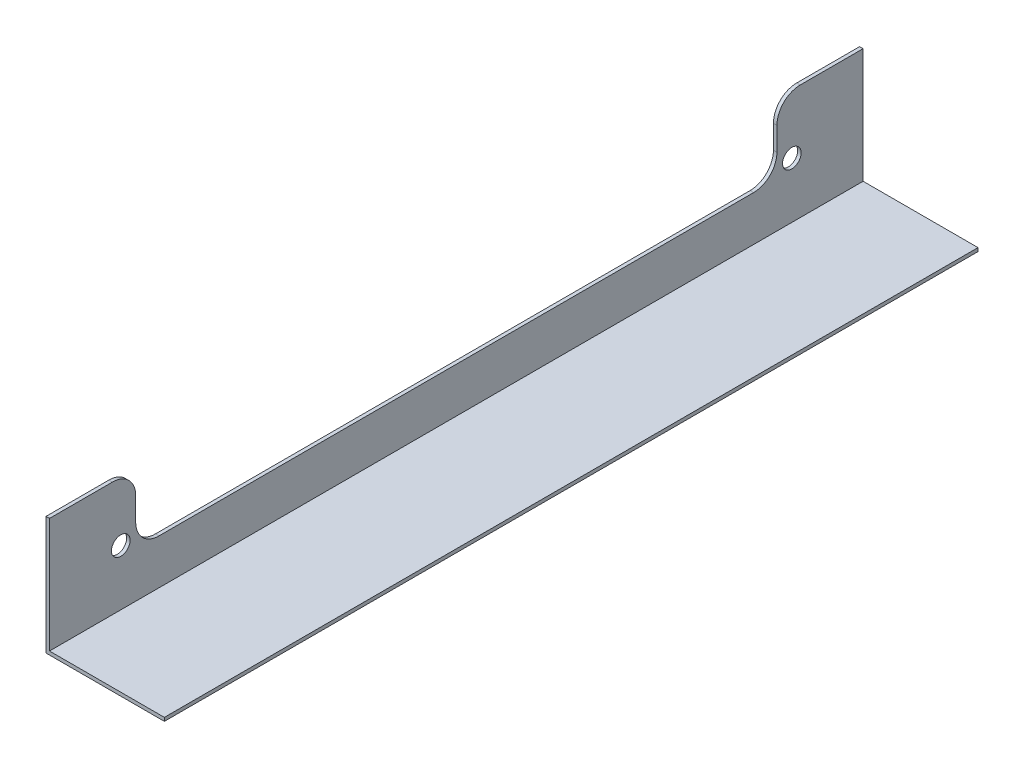
SolidWorks part; units mm, degrees
material "AISI 1015 Acero estirado en frío (SS)"
ref_plane "Alzado" through (0, 0, 0) normal (0, 0, 1) x (1, 0, 0)
ref_plane "Planta" through (0, 0, 0) normal (0, 1, 0) x (1, 0, 0)
ref_plane "Vista lateral" through (0, 0, 0) normal (1, 0, 0) x (0, 0, -1)
sketch "Croquis1" plane through (0, 0, 0) normal (0, 0, 1) x (1, 0, 0)
  line L0 (0, 0) -> (0, 50.8)
  line L1 (0, 0) -> (50.8, 0)
  line L2 (1.5, 1.5) -> (50.8, 1.5)
  line L3 (1.5, 1.5) -> (1.5, 50.8)
  line L4 (1.5, 50.8) -> (0, 50.8)
  line L5 (50.8, 1.5) -> (50.8, 0)
  dimension "D1" = 50.8
  dimension "D2" = 1.5
extrude "Saliente-Extruir1" add sketch "Croquis1" along normal blind 349.2
sketch "Croquis2" plane through (0, 0, 0) normal (-1, 0, 0) x (0, 0, 1)
  line L0 (349.2, 25.4) -> (-34.0342, 25.4) construction
  line L1 (349.2, 50.8) -> (349.2, 0) construction
  line L2 (174.6, 0) -> (174.6, 64.0617) construction
  line L3 (349.2, 0) -> (0, 0) construction
  circle A0 centre (126.6, 25.4) radius 4
  circle A1 centre (222.6, 25.4) radius 4
  circle A2 centre (30.6, 25.4) radius 4
  circle A3 centre (318.6, 25.4) radius 4
  dimension "D1" = 8
  dimension "D2" = 48
  dimension "D3" = 48
  dimension "D4" = 96
  dimension "D5" = 96
extrude "Cortar-Extruir1" cut sketch "Croquis2" against normal blind 2
sketch "Croquis5" plane through (0, 0, 0) normal (-1, 0, 0) x (0, 0, 1)
  line L0 (174.6, 0) -> (174.6, 50.8) construction
  line L1 (349.2, 0) -> (0, 0) construction
  line L2 (349.2, 50.8) -> (0, 50.8) construction
  line L3 (312.2, 0) -> (312.2, 50.8) construction
  line L4 (349.2, 50.8) -> (349.2, 0) construction
  line L5 (349.2, 20.8) -> (0, 20.8) construction
  line L6 (0, 50.8) -> (0, 0) construction
  line L7 (312.2, 50.8) -> (312.2, 20.8)
  line L8 (312.2, 20.8) -> (37, 20.8)
  line L9 (37, 50.8) -> (37, 20.8)
  point P16 (174.6, 20.8)
  dimension "D1" = 37
  dimension "D2" = 30
extrude "Cortar-Extruir2" cut sketch "Croquis5" against normal blind 2 and the other way through all
fillet "Redondeo1" radius 10 4 edges at (0.75, 50.8, 37) (0.75, 20.8, 37) (0.75, 50.8, 312.2) (0.75, 20.8, 312.2)
